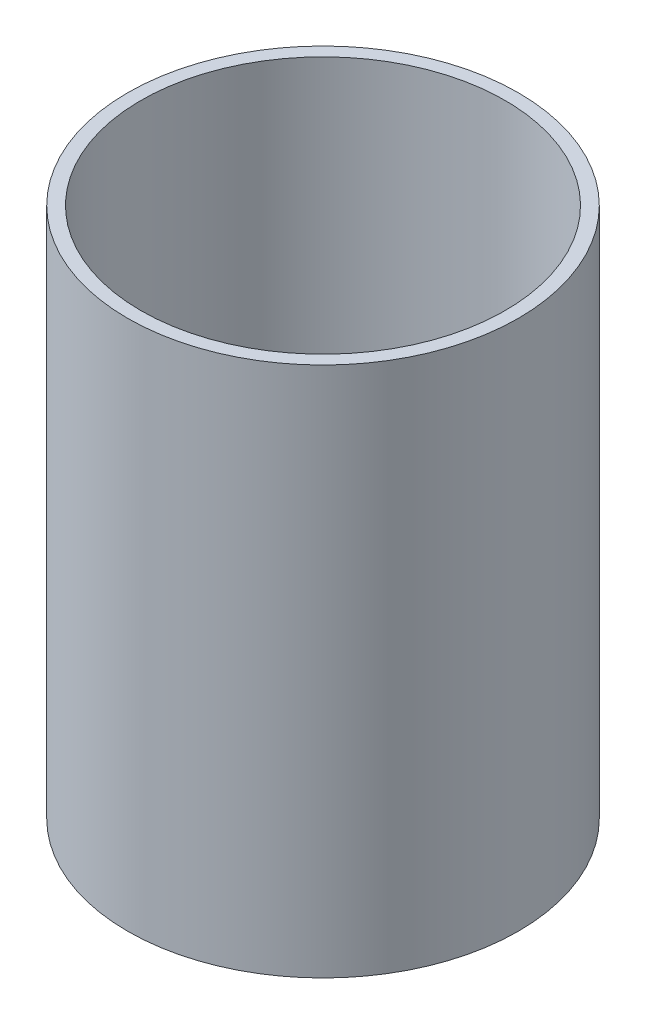
SolidWorks part; units mm, degrees
ref_plane "Plan de face" through (0, 0, 0) normal (0, 0, 1) x (1, 0, 0)
ref_plane "Plan de dessus" through (0, 0, 0) normal (0, 1, 0) x (1, 0, 0)
ref_plane "Plan de droite" through (0, 0, 0) normal (1, 0, 0) x (0, 0, -1)
sketch "Esquisse1" plane through (0, 0, 0) normal (0, 1, 0) x (1, 0, 0)
  circle A0 centre (0, 0) radius 73.61
  circle A1 centre (0, 0) radius 68.61
  dimension "D1" = 147.22
  dimension "D2" = 5
extrude "Boss.-Extru.1" add sketch "Esquisse1" along normal blind 200
ref_plane "Plan1" through (0, 100, 0) normal (0, -1, 0) x (-1, 0, 0)
